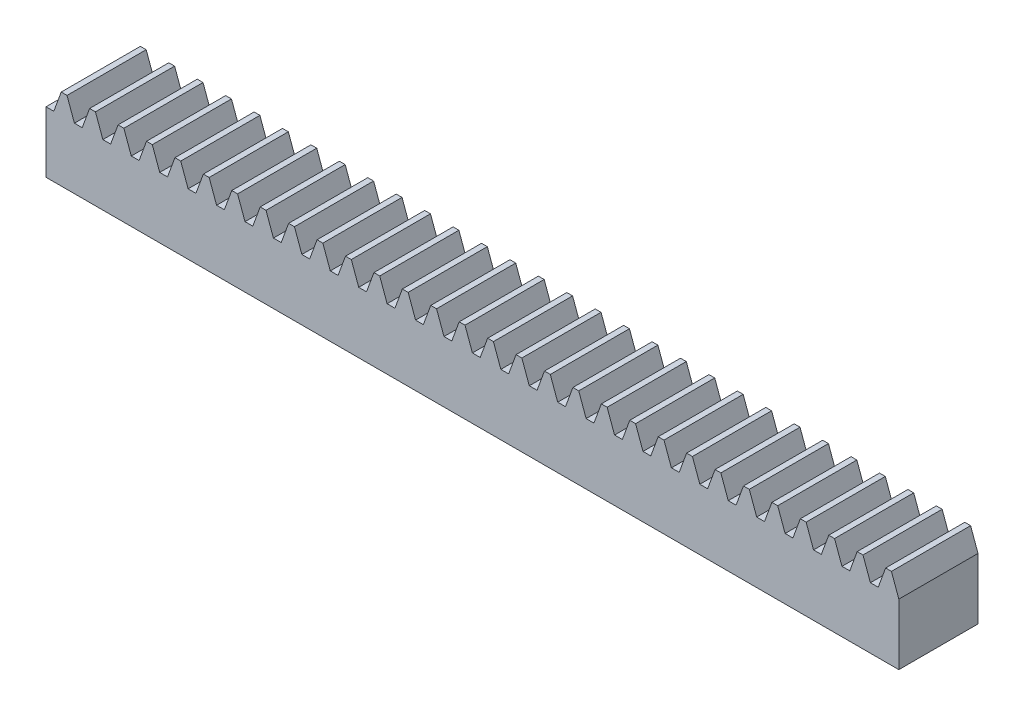
SolidWorks part; units mm, degrees
extrude "Blank" add sketch "BlankSke" against normal blind 20
sketch "BlankSke" plane through (0, 0, 0) normal (0, 0, 1) x (1, 0, 0)
  line L1 (0, 0) -> (500, 0)
  line L2 (0, 0) -> (0, 45)
  line L3 (0, 45) -> (500, 45)
  line L4 (500, 0) -> (500, 45)
  dimension "Length" = 500
material "Ottone"
ref_plane "Plane1" through (0, 0, 0) normal (0, 0, 1) x (1, 0, 0)
ref_plane "Plane2" through (0, 0, 0) normal (0, 1, 0) x (1, 0, 0)
ref_plane "Plane3" through (0, 0, 0) normal (1, 0, 0) x (0, 0, -1)
sketch "HoldingSke" plane through (0, 0, 0) normal (0, 1, 0) x (1, 0, 0)
  line L0 (0, 0) -> (0.0278, 0.1981)
  line L1 (-15, 0) -> (100, 0) construction
  line L2 (0, 0) -> (-2.1039, 2.3779)
  line L3 (0, 0) -> (-11.863, 4.5341)
  line L4 (0, 0) -> (7.2428, 4.7035)
  line L5 (0, 0) -> (-23.7986, -8.8762)
  line L6 (0, 0) -> (-10.5278, -7.1032)
  line L9 (-71.009, 38.7566) -> (398.8373, 209.7667)
  line L10 (-76.2, 7.3779) -> (-36.2, 7.3779)
  line L11 (0, 0) -> (-20, 0)
  line L12 (-76.2, 101.6) -> (-76.033, 101.6)
  line L13 (24.9733, 27.94) -> (52.9518, 28.4284)
  line L14 (24.9733, 27.94) -> (24.9743, 27.94)
  line L15 (24.9733, 27.94) -> (100.4006, 29.5858)
  circle A0 centre (0, 0) radius 19.05
  circle A1 centre (0, 0) radius 20
  circle A2 centre (0, 0) radius 12.7
  dimension "Num_teeth" = 33
  dimension "Width" = 20
  dimension "Length" = 500
  dimension "Pitch_height" = 40
sketch "TooCutSkeIll" plane through (0, 0, 0) normal (0, 0, 1) x (1, 0, 0)
  line L0 (-6.1999, 44.8684) -> (-2.4528, 34.5731)
  line L1 (-1.2772, 33.75) -> (1.2772, 33.75)
  line L2 (2.4528, 34.5731) -> (6.1999, 44.8684)
  line L3 (500, 45) -> (0, 45) construction
  line L4 (0, 0) -> (0, 64.897) construction
  line L5 (-13.208, 40) -> (12.954, 40) construction
  line L6 (0, 0) -> (500, 0) construction
  line L7 (4.428, 40) -> (4.428, 48.7463) construction
  line L8 (-4.428, 40) -> (-4.428, 48.7463) construction
  line L9 (6.3879, 45) -> (6.3879, 45.0254)
  line L10 (-6.3879, 45) -> (-6.3879, 45.0254)
  line L11 (-6.3879, 45.0254) -> (6.3879, 45.0254)
  arc A0 (1.2772, 33.75) -> (2.4528, 34.5731) centre (1.2772, 35.001) ccw
  arc A1 (-2.4528, 34.5731) -> (-1.2772, 33.75) centre (-1.2772, 35.001) ccw
  arc A2 (6.3879, 45) -> (6.1999, 44.8684) centre (6.3879, 44.8) ccw
  arc A3 (-6.1999, 44.8684) -> (-6.3879, 45) centre (-6.3879, 44.8) ccw
  dimension "Addendum_plus" = 5.0254
  dimension "Pitch_height" = 40
  dimension "Pressure_angle" = 20
  dimension "Gap_width" = 8.856
  dimension "Dedendum" = 6.25
extrude "ToothCutIll" [suppressed] cut sketch "TooCutSkeIll" against normal through all
sketch "TooCutSkeSim" plane through (0, 0, 0) normal (0, 0, 1) x (1, 0, 0)
  line L0 (2.1532, 33.75) -> (-2.1532, 33.75)
  line L1 (6.2571, 45.0254) -> (2.1532, 33.75)
  line L2 (0, 17.4625) -> (0, 53.467) construction
  line L3 (6.2571, 45.0254) -> (-6.2571, 45.0254)
  line L6 (-6.2571, 45.0254) -> (-2.1532, 33.75)
  line L9 (-4.428, 40) -> (4.428, 40) construction
  line L10 (0, 0) -> (500, 0) construction
  line L11 (4.428, 40) -> (4.428, 53.467) construction
  line L12 (-4.428, 40) -> (-4.428, 53.467) construction
  dimension "Addendum_plus" = 5.0254
  dimension "Pitch_height" = 40
  dimension "Pressure_angle" = 20
  dimension "Gap_width" = 8.856
  dimension "Dedendum" = 6.25
extrude "ToothCutSim" cut sketch "TooCutSkeSim" against normal through all
pattern_linear "TeethCuts" count 33 spacing 15.708 along (1, 0, 0) of "ToothCutSim"
scale "Scala1" scale about centroid uniform scaling yes scale factor 0.16
sketch "Schizzo1" plane through (0, 0, -8.4) normal (0, 0, 1) x (1, 0, 0)
  line L131 (290.1466, 16.6046) -> (290.1466, 22.2251)
  line L132 (290.1466, 22.2251) -> (289.5718, 23.8046)
  line L133 (289.5718, 23.8046) -> (289.0578, 23.8046)
  line L134 (289.0578, 23.8046) -> (288.4027, 22.0046)
  line L135 (288.4027, 22.0046) -> (287.7136, 22.0046)
  line L136 (287.7136, 22.0046) -> (287.0585, 23.8046)
  line L137 (287.0585, 23.8046) -> (286.5445, 23.8046)
  line L138 (286.5445, 23.8046) -> (285.8894, 22.0046)
  line L139 (285.8894, 22.0046) -> (285.2004, 22.0046)
  line L140 (285.2004, 22.0046) -> (284.5452, 23.8046)
  line L141 (284.5452, 23.8046) -> (284.0313, 23.8046)
  line L142 (284.0313, 23.8046) -> (283.3761, 22.0046)
  line L143 (283.3761, 22.0046) -> (282.6871, 22.0046)
  line L144 (282.6871, 22.0046) -> (282.0319, 23.8046)
  line L145 (282.0319, 23.8046) -> (281.518, 23.8046)
  line L146 (281.518, 23.8046) -> (280.8628, 22.0046)
  line L147 (280.8628, 22.0046) -> (280.1738, 22.0046)
  line L148 (280.1738, 22.0046) -> (279.5187, 23.8046)
  line L149 (279.5187, 23.8046) -> (279.0047, 23.8046)
  line L150 (279.0047, 23.8046) -> (278.3496, 22.0046)
  line L151 (278.3496, 22.0046) -> (277.6605, 22.0046)
  line L152 (277.6605, 22.0046) -> (277.0054, 23.8046)
  line L153 (277.0054, 23.8046) -> (276.4914, 23.8046)
  line L154 (276.4914, 23.8046) -> (275.8363, 22.0046)
  line L155 (275.8363, 22.0046) -> (275.1473, 22.0046)
  line L156 (275.1473, 22.0046) -> (274.4921, 23.8046)
  line L157 (274.4921, 23.8046) -> (273.9782, 23.8046)
  line L158 (273.9782, 23.8046) -> (273.323, 22.0046)
  line L159 (273.323, 22.0046) -> (272.634, 22.0046)
  line L160 (272.634, 22.0046) -> (271.9788, 23.8046)
  line L161 (271.9788, 23.8046) -> (271.4649, 23.8046)
  line L162 (271.4649, 23.8046) -> (270.8097, 22.0046)
  line L163 (270.8097, 22.0046) -> (270.1207, 22.0046)
  line L164 (270.1207, 22.0046) -> (269.4656, 23.8046)
  line L165 (269.4656, 23.8046) -> (268.9516, 23.8046)
  line L166 (268.9516, 23.8046) -> (268.2965, 22.0046)
  line L167 (268.2965, 22.0046) -> (267.6074, 22.0046)
  line L168 (267.6074, 22.0046) -> (266.9523, 23.8046)
  line L169 (266.9523, 23.8046) -> (266.4383, 23.8046)
  line L170 (266.4383, 23.8046) -> (265.7832, 22.0046)
  line L171 (265.7832, 22.0046) -> (265.0942, 22.0046)
  line L172 (265.0942, 22.0046) -> (264.439, 23.8046)
  line L173 (264.439, 23.8046) -> (263.9251, 23.8046)
  line L174 (263.9251, 23.8046) -> (263.2699, 22.0046)
  line L175 (263.2699, 22.0046) -> (262.5809, 22.0046)
  line L176 (262.5809, 22.0046) -> (261.9258, 23.8046)
  line L177 (261.9258, 23.8046) -> (261.4118, 23.8046)
  line L178 (261.4118, 23.8046) -> (260.7566, 22.0046)
  line L179 (260.7566, 22.0046) -> (260.0676, 22.0046)
  line L180 (260.0676, 22.0046) -> (259.4125, 23.8046)
  line L181 (259.4125, 23.8046) -> (258.8985, 23.8046)
  line L182 (258.8985, 23.8046) -> (258.2434, 22.0046)
  line L183 (258.2434, 22.0046) -> (257.5543, 22.0046)
  line L184 (257.5543, 22.0046) -> (256.8992, 23.8046)
  line L185 (256.8992, 23.8046) -> (256.3852, 23.8046)
  line L186 (256.3852, 23.8046) -> (255.7301, 22.0046)
  line L187 (255.7301, 22.0046) -> (255.0411, 22.0046)
  line L188 (255.0411, 22.0046) -> (254.3859, 23.8046)
  line L189 (254.3859, 23.8046) -> (253.872, 23.8046)
  line L190 (253.872, 23.8046) -> (253.2168, 22.0046)
  line L191 (253.2168, 22.0046) -> (252.5278, 22.0046)
  line L192 (252.5278, 22.0046) -> (251.8727, 23.8046)
  line L193 (251.8727, 23.8046) -> (251.3587, 23.8046)
  line L194 (251.3587, 23.8046) -> (250.7035, 22.0046)
  line L195 (250.7035, 22.0046) -> (250.0145, 22.0046)
  line L196 (250.0145, 22.0046) -> (249.3594, 23.8046)
  line L197 (249.3594, 23.8046) -> (248.8454, 23.8046)
  line L198 (248.8454, 23.8046) -> (248.1903, 22.0046)
  line L199 (248.1903, 22.0046) -> (247.5013, 22.0046)
  line L200 (247.5013, 22.0046) -> (246.8461, 23.8046)
  line L201 (246.8461, 23.8046) -> (246.3321, 23.8046)
  line L202 (246.3321, 23.8046) -> (245.677, 22.0046)
  line L203 (245.677, 22.0046) -> (244.988, 22.0046)
  line L204 (244.988, 22.0046) -> (244.3328, 23.8046)
  line L205 (244.3328, 23.8046) -> (243.8189, 23.8046)
  line L206 (243.8189, 23.8046) -> (243.1637, 22.0046)
  line L207 (243.1637, 22.0046) -> (242.4747, 22.0046)
  line L208 (242.4747, 22.0046) -> (241.8196, 23.8046)
  line L209 (241.8196, 23.8046) -> (241.3056, 23.8046)
  line L210 (241.3056, 23.8046) -> (240.6504, 22.0046)
  line L211 (240.6504, 22.0046) -> (239.9614, 22.0046)
  line L212 (239.9614, 22.0046) -> (239.3063, 23.8046)
  line L213 (239.3063, 23.8046) -> (238.7923, 23.8046)
  line L214 (238.7923, 23.8046) -> (238.1372, 22.0046)
  line L215 (238.1372, 22.0046) -> (237.4482, 22.0046)
  line L216 (237.4482, 22.0046) -> (236.793, 23.8046)
  line L217 (236.793, 23.8046) -> (236.279, 23.8046)
  line L218 (236.279, 23.8046) -> (235.6239, 22.0046)
  line L219 (235.6239, 22.0046) -> (234.9349, 22.0046)
  line L220 (234.9349, 22.0046) -> (234.2797, 23.8046)
  line L221 (234.2797, 23.8046) -> (233.7658, 23.8046)
  line L222 (233.7658, 23.8046) -> (233.1106, 22.0046)
  line L223 (233.1106, 22.0046) -> (232.4216, 22.0046)
  line L224 (232.4216, 22.0046) -> (231.7665, 23.8046)
  line L225 (231.7665, 23.8046) -> (231.2525, 23.8046)
  line L226 (231.2525, 23.8046) -> (230.5974, 22.0046)
  line L227 (230.5974, 22.0046) -> (229.9083, 22.0046)
  line L228 (229.9083, 22.0046) -> (229.2532, 23.8046)
  line L229 (229.2532, 23.8046) -> (228.7392, 23.8046)
  line L230 (228.7392, 23.8046) -> (228.0841, 22.0046)
  line L231 (228.0841, 22.0046) -> (227.3951, 22.0046)
  line L232 (227.3951, 22.0046) -> (226.7399, 23.8046)
  line L233 (226.7399, 23.8046) -> (226.2259, 23.8046)
  line L234 (226.2259, 23.8046) -> (225.5708, 22.0046)
  line L235 (225.5708, 22.0046) -> (224.8818, 22.0046)
  line L236 (224.8818, 22.0046) -> (224.2266, 23.8046)
  line L237 (224.2266, 23.8046) -> (223.7127, 23.8046)
  line L238 (223.7127, 23.8046) -> (223.0575, 22.0046)
  line L239 (223.0575, 22.0046) -> (222.3685, 22.0046)
  line L240 (222.3685, 22.0046) -> (221.7134, 23.8046)
  line L241 (221.7134, 23.8046) -> (221.1994, 23.8046)
  line L242 (221.1994, 23.8046) -> (220.5443, 22.0046)
  line L243 (220.5443, 22.0046) -> (219.8552, 22.0046)
  line L244 (219.8552, 22.0046) -> (219.2001, 23.8046)
  line L245 (219.2001, 23.8046) -> (218.6861, 23.8046)
  line L246 (218.6861, 23.8046) -> (218.031, 22.0046)
  line L247 (218.031, 22.0046) -> (217.342, 22.0046)
  line L248 (217.342, 22.0046) -> (216.6868, 23.8046)
  line L249 (216.6868, 23.8046) -> (216.1729, 23.8046)
  line L250 (216.1729, 23.8046) -> (215.5177, 22.0046)
  line L251 (215.5177, 22.0046) -> (214.8287, 22.0046)
  line L252 (214.8287, 22.0046) -> (214.1735, 23.8046)
  line L253 (214.1735, 23.8046) -> (213.6596, 23.8046)
  line L254 (213.6596, 23.8046) -> (213.0044, 22.0046)
  line L255 (213.0044, 22.0046) -> (212.3154, 22.0046)
  line L256 (212.3154, 22.0046) -> (211.6603, 23.8046)
  line L257 (211.6603, 23.8046) -> (211.1463, 23.8046)
  line L258 (211.1463, 23.8046) -> (210.4912, 22.0046)
  line L259 (210.4912, 22.0046) -> (210.1466, 22.0046)
  line L260 (210.1466, 22.0046) -> (210.1466, 16.6046)
  line L261 (210.1466, 16.6046) -> (290.1466, 16.6046)
  line L262 (290.1466, 16.6046) -> (290.1466, 22.2251)
  line L263 (290.1466, 22.2251) -> (289.5718, 23.8046)
  line L264 (289.5718, 23.8046) -> (289.0578, 23.8046)
  line L265 (289.0578, 23.8046) -> (288.4027, 22.0046)
  line L266 (288.4027, 22.0046) -> (287.7136, 22.0046)
  line L267 (287.7136, 22.0046) -> (287.0585, 23.8046)
  line L268 (287.0585, 23.8046) -> (286.5445, 23.8046)
  line L269 (286.5445, 23.8046) -> (285.8894, 22.0046)
  line L270 (285.8894, 22.0046) -> (285.2004, 22.0046)
  line L271 (285.2004, 22.0046) -> (284.5452, 23.8046)
  line L272 (284.5452, 23.8046) -> (284.0313, 23.8046)
  line L273 (284.0313, 23.8046) -> (283.3761, 22.0046)
  line L274 (283.3761, 22.0046) -> (282.6871, 22.0046)
  line L275 (282.6871, 22.0046) -> (282.0319, 23.8046)
  line L276 (282.0319, 23.8046) -> (281.518, 23.8046)
  line L277 (281.518, 23.8046) -> (280.8628, 22.0046)
  line L278 (280.8628, 22.0046) -> (280.1738, 22.0046)
  line L279 (280.1738, 22.0046) -> (279.5187, 23.8046)
  line L280 (279.5187, 23.8046) -> (279.0047, 23.8046)
  line L281 (279.0047, 23.8046) -> (278.3496, 22.0046)
  line L282 (278.3496, 22.0046) -> (277.6605, 22.0046)
  line L283 (277.6605, 22.0046) -> (277.0054, 23.8046)
  line L284 (277.0054, 23.8046) -> (276.4914, 23.8046)
  line L285 (276.4914, 23.8046) -> (275.8363, 22.0046)
  line L286 (275.8363, 22.0046) -> (275.1473, 22.0046)
  line L287 (275.1473, 22.0046) -> (274.4921, 23.8046)
  line L288 (274.4921, 23.8046) -> (273.9782, 23.8046)
  line L289 (273.9782, 23.8046) -> (273.323, 22.0046)
  line L290 (273.323, 22.0046) -> (272.634, 22.0046)
  line L291 (272.634, 22.0046) -> (271.9788, 23.8046)
  line L292 (271.9788, 23.8046) -> (271.4649, 23.8046)
  line L293 (271.4649, 23.8046) -> (270.8097, 22.0046)
  line L294 (270.8097, 22.0046) -> (270.1207, 22.0046)
  line L295 (270.1207, 22.0046) -> (269.4656, 23.8046)
  line L296 (269.4656, 23.8046) -> (268.9516, 23.8046)
  line L297 (268.9516, 23.8046) -> (268.2965, 22.0046)
  line L298 (268.2965, 22.0046) -> (267.6074, 22.0046)
  line L299 (267.6074, 22.0046) -> (266.9523, 23.8046)
  line L300 (266.9523, 23.8046) -> (266.4383, 23.8046)
  line L301 (266.4383, 23.8046) -> (265.7832, 22.0046)
  line L302 (265.7832, 22.0046) -> (265.0942, 22.0046)
  line L303 (265.0942, 22.0046) -> (264.439, 23.8046)
  line L304 (264.439, 23.8046) -> (263.9251, 23.8046)
  line L305 (263.9251, 23.8046) -> (263.2699, 22.0046)
  line L306 (263.2699, 22.0046) -> (262.5809, 22.0046)
  line L307 (262.5809, 22.0046) -> (261.9258, 23.8046)
  line L308 (261.9258, 23.8046) -> (261.4118, 23.8046)
  line L309 (261.4118, 23.8046) -> (260.7566, 22.0046)
  line L310 (260.7566, 22.0046) -> (260.0676, 22.0046)
  line L311 (260.0676, 22.0046) -> (259.4125, 23.8046)
  line L312 (259.4125, 23.8046) -> (258.8985, 23.8046)
  line L313 (258.8985, 23.8046) -> (258.2434, 22.0046)
  line L314 (258.2434, 22.0046) -> (257.5543, 22.0046)
  line L315 (257.5543, 22.0046) -> (256.8992, 23.8046)
  line L316 (256.8992, 23.8046) -> (256.3852, 23.8046)
  line L317 (256.3852, 23.8046) -> (255.7301, 22.0046)
  line L318 (255.7301, 22.0046) -> (255.0411, 22.0046)
  line L319 (255.0411, 22.0046) -> (254.3859, 23.8046)
  line L320 (254.3859, 23.8046) -> (253.872, 23.8046)
  line L321 (253.872, 23.8046) -> (253.2168, 22.0046)
  line L322 (253.2168, 22.0046) -> (252.5278, 22.0046)
  line L323 (252.5278, 22.0046) -> (251.8727, 23.8046)
  line L324 (251.8727, 23.8046) -> (251.3587, 23.8046)
  line L325 (251.3587, 23.8046) -> (250.7035, 22.0046)
  line L326 (250.7035, 22.0046) -> (250.0145, 22.0046)
  line L327 (250.0145, 22.0046) -> (249.3594, 23.8046)
  line L328 (249.3594, 23.8046) -> (248.8454, 23.8046)
  line L329 (248.8454, 23.8046) -> (248.1903, 22.0046)
  line L330 (248.1903, 22.0046) -> (247.5013, 22.0046)
  line L331 (247.5013, 22.0046) -> (246.8461, 23.8046)
  line L332 (246.8461, 23.8046) -> (246.3321, 23.8046)
  line L333 (246.3321, 23.8046) -> (245.677, 22.0046)
  line L334 (245.677, 22.0046) -> (244.988, 22.0046)
  line L335 (244.988, 22.0046) -> (244.3328, 23.8046)
  line L336 (244.3328, 23.8046) -> (243.8189, 23.8046)
  line L337 (243.8189, 23.8046) -> (243.1637, 22.0046)
  line L338 (243.1637, 22.0046) -> (242.4747, 22.0046)
  line L339 (242.4747, 22.0046) -> (241.8196, 23.8046)
  line L340 (241.8196, 23.8046) -> (241.3056, 23.8046)
  line L341 (241.3056, 23.8046) -> (240.6504, 22.0046)
  line L342 (240.6504, 22.0046) -> (239.9614, 22.0046)
  line L343 (239.9614, 22.0046) -> (239.3063, 23.8046)
  line L344 (239.3063, 23.8046) -> (238.7923, 23.8046)
  line L345 (238.7923, 23.8046) -> (238.1372, 22.0046)
  line L346 (238.1372, 22.0046) -> (237.4482, 22.0046)
  line L347 (237.4482, 22.0046) -> (236.793, 23.8046)
  line L348 (236.793, 23.8046) -> (236.279, 23.8046)
  line L349 (236.279, 23.8046) -> (235.6239, 22.0046)
  line L350 (235.6239, 22.0046) -> (234.9349, 22.0046)
  line L351 (234.9349, 22.0046) -> (234.2797, 23.8046)
  line L352 (234.2797, 23.8046) -> (233.7658, 23.8046)
  line L353 (233.7658, 23.8046) -> (233.1106, 22.0046)
  line L354 (233.1106, 22.0046) -> (232.4216, 22.0046)
  line L355 (232.4216, 22.0046) -> (231.7665, 23.8046)
  line L356 (231.7665, 23.8046) -> (231.2525, 23.8046)
  line L357 (231.2525, 23.8046) -> (230.5974, 22.0046)
  line L358 (230.5974, 22.0046) -> (229.9083, 22.0046)
  line L359 (229.9083, 22.0046) -> (229.2532, 23.8046)
  line L360 (229.2532, 23.8046) -> (228.7392, 23.8046)
  line L361 (228.7392, 23.8046) -> (228.0841, 22.0046)
  line L362 (228.0841, 22.0046) -> (227.3951, 22.0046)
  line L363 (227.3951, 22.0046) -> (226.7399, 23.8046)
  line L364 (226.7399, 23.8046) -> (226.2259, 23.8046)
  line L365 (226.2259, 23.8046) -> (225.5708, 22.0046)
  line L366 (225.5708, 22.0046) -> (224.8818, 22.0046)
  line L367 (224.8818, 22.0046) -> (224.2266, 23.8046)
  line L368 (224.2266, 23.8046) -> (223.7127, 23.8046)
  line L369 (223.7127, 23.8046) -> (223.0575, 22.0046)
  line L370 (223.0575, 22.0046) -> (222.3685, 22.0046)
  line L371 (222.3685, 22.0046) -> (221.7134, 23.8046)
  line L372 (221.7134, 23.8046) -> (221.1994, 23.8046)
  line L373 (221.1994, 23.8046) -> (220.5443, 22.0046)
  line L374 (220.5443, 22.0046) -> (219.8552, 22.0046)
  line L375 (219.8552, 22.0046) -> (219.2001, 23.8046)
  line L376 (219.2001, 23.8046) -> (218.6861, 23.8046)
  line L377 (218.6861, 23.8046) -> (218.031, 22.0046)
  line L378 (218.031, 22.0046) -> (217.342, 22.0046)
  line L379 (217.342, 22.0046) -> (216.6868, 23.8046)
  line L380 (216.6868, 23.8046) -> (216.1729, 23.8046)
  line L381 (216.1729, 23.8046) -> (215.5177, 22.0046)
  line L382 (215.5177, 22.0046) -> (214.8287, 22.0046)
  line L383 (214.8287, 22.0046) -> (214.1735, 23.8046)
  line L384 (214.1735, 23.8046) -> (213.6596, 23.8046)
  line L385 (213.6596, 23.8046) -> (213.0044, 22.0046)
  line L386 (213.0044, 22.0046) -> (212.3154, 22.0046)
  line L387 (212.3154, 22.0046) -> (211.6603, 23.8046)
  line L388 (211.6603, 23.8046) -> (211.1463, 23.8046)
  line L389 (211.1463, 23.8046) -> (210.4912, 22.0046)
  line L390 (210.4912, 22.0046) -> (210.1466, 22.0046)
  line L391 (210.1466, 22.0046) -> (210.1466, 16.6046)
  line L392 (210.1466, 16.6046) -> (290.1466, 16.6046)
  dimension "D1" = 0
extrude "Estrusione-Estrusione1" add sketch "Schizzo1" along normal blind 3.8
sketch "Schizzo2" plane through (0, 22.0046, 0) normal (0, 1, 0) x (1, 0, 0)
  line L0 (212.3154, 11.6) -> (212.3154, 4.6)
  line L1 (212.3154, 4.6) -> (208.4622, 2.3479)
  line L2 (208.4622, 2.3479) -> (205.8972, 4.6)
  line L3 (205.8972, 4.6) -> (205.1103, 10.2116)
  line L4 (205.1103, 10.2116) -> (209.7344, 15.7205)
  line L5 (209.7344, 15.7205) -> (212.2339, 13.5258)
  line L6 (212.2339, 13.5258) -> (212.3154, 11.6)
extrude "Taglio-Estrusione2" cut sketch "Schizzo2" along normal mid plane 20
sketch "Schizzo3" plane through (0, 22.0046, 0) normal (0, 1, 0) x (1, 0, 0)
  line L0 (287.7136, 4.6) -> (287.7136, 11.6)
  line L1 (287.7136, 11.6) -> (292.7917, 17.742)
  line L2 (292.7917, 17.742) -> (298.0933, 11.1699)
  line L3 (298.0933, 11.1699) -> (295.2064, 3.5985)
  line L4 (295.2064, 3.5985) -> (291.0834, 1.0336)
  line L5 (291.0834, 1.0336) -> (287.7136, 3.8195)
  line L6 (287.7136, 3.8195) -> (287.7136, 4.6)
extrude "Taglio-Estrusione3" cut sketch "Schizzo3" against normal mid plane 20
pattern_linear "Ripetizione a L1" [suppressed] count 2 spacing 75.3982 of bodies 107 105
equation "' \"Module@HoldingSke\" = 6.35"
equation "' \"Num_teeth@HoldingSke\" = 12"
equation "' \"Ap@HoldingSke\" =  20"
equation "' \"Ap@HoldingSke\" = 20"
equation "' \"Width@HoldingSke\" = 0.25 * 25.4"
equation "' \"Show_teeth@HoldingSke\" = 500"
equation "' \"Backlash@HoldingSke\" = 0.009 * 25.4"
equation "' \"Addendum_fac@HoldingSke\" = 1.0"
equation "' \"Dedendum_fac@HoldingSke\" = 1.25"
equation "' \"Dedendum_add@HoldingSke\" = 0.00005 * 25.4"
equation "' \"Clearance_fac@HoldingSke\" = 0.25"
equation "' \"Pitch_height@HoldingSke\" = 1 * 25.4"
equation "' \"Length@HoldingSke\" = 4.71 * 25.4"
equation "\"Pitch@HoldingSke\" = 1 / \"Module@HoldingSke\""
equation "\"MPH@HoldingSke\" = \"Dedendum_fac@HoldingSke\" / \"Pitch@HoldingSke\" + 2 * \"Dedendum_add@HoldingSke\" + 0.002 * 25.4"
equation "\"MPH@HoldingSke\" = ((sgn( \"MPH@HoldingSke\" - \"Pitch_height@HoldingSke\")+1)*( \"MPH@HoldingSke\" - \"Pitch_height@HoldingSke\"))/2 + \"Pitch_height@HoldingSke\""
equation "\"Blank_height@BlankSke\" = \"Pitch_height@HoldingSke\" + \"Addendum_fac@HoldingSke\"  / \"Pitch@HoldingSke\" "
equation "\"Length@BlankSke\" =  \"Length@HoldingSke\""
equation "\"Face_width@Blank\" = \"Width@HoldingSke\""
equation "\"Pressure_angle@TooCutSkeIll\" = \"Ap@HoldingSke\""
equation "\"Addendum_plus@TooCutSkeIll\" =  \"Addendum_fac@HoldingSke\"  / \"Pitch@HoldingSke\" + 0.001 *25.4"
equation "\"Dedendum@TooCutSkeIll\" = \"Dedendum_fac@HoldingSke\"  / \"Pitch@HoldingSke\""
equation "\"Pitch_height@TooCutSkeIll\" =  \"MPH@HoldingSke\""
equation "\"Gap_width@TooCutSkeIll\" = 3.14159265 / 2 / \"Pitch@HoldingSke\" + 6 * \"Backlash@HoldingSke\""
equation "\"Pressure_angle@TooCutSkeSim\" = \"Ap@HoldingSke\""
equation "\"Addendum_plus@TooCutSkeSim\" =  \"Addendum_fac@HoldingSke\"  / \"Pitch@HoldingSke\" + 0.001 * 25.4"
equation "\"Dedendum@TooCutSkeSim\" = \"Dedendum_fac@HoldingSke\"  / \"Pitch@HoldingSke\""
equation "\"Pitch_height@TooCutSkeSim\" =  \"MPH@HoldingSke\""
equation "\"Gap_width@TooCutSkeSim\" = 3.14159265 / 2 / \"Pitch@HoldingSke\" + 6 * \"Backlash@HoldingSke\""
equation "\"Root_fillet@TooCutSkeIll\" = \"Clearance_fac@HoldingSke\" / \"Pitch@HoldingSke\" + \"Dedendum_add@HoldingSke\""
equation "\"Break_rad@TooCutSkeIll\" = 0.02 / \"Pitch@HoldingSke\" * 2"
equation "\"Linear_pitch@TeethCuts\" = 3.14159265 / \"Pitch@HoldingSke\""
equation "\"Num_teeth@HoldingSke\" = int( ( \"Length@HoldingSke\" + 0 ) / (3.14159265 / \"Pitch@HoldingSke\")) + 0.9999  + 1"
equation " \"Num_teeth@TeethCuts\" = int( \"Show_teeth@HoldingSke\" ) + 1"
equation " \"Num_teeth@TeethCuts\" = ((sgn( \"Num_teeth@TeethCuts\" - \"Num_teeth@HoldingSke\" )-1)*( \"Num_teeth@TeethCuts\" - \"Num_teeth@HoldingSke\" ))/-2+ \"Num_teeth@HoldingSke\""
equation " \"Num_teeth@TeethCuts\" = ((sgn( \"Num_teeth@TeethCuts\" - 2.0)+1)*( \"Num_teeth@TeethCuts\" - 2.0))/2 +2.0"
